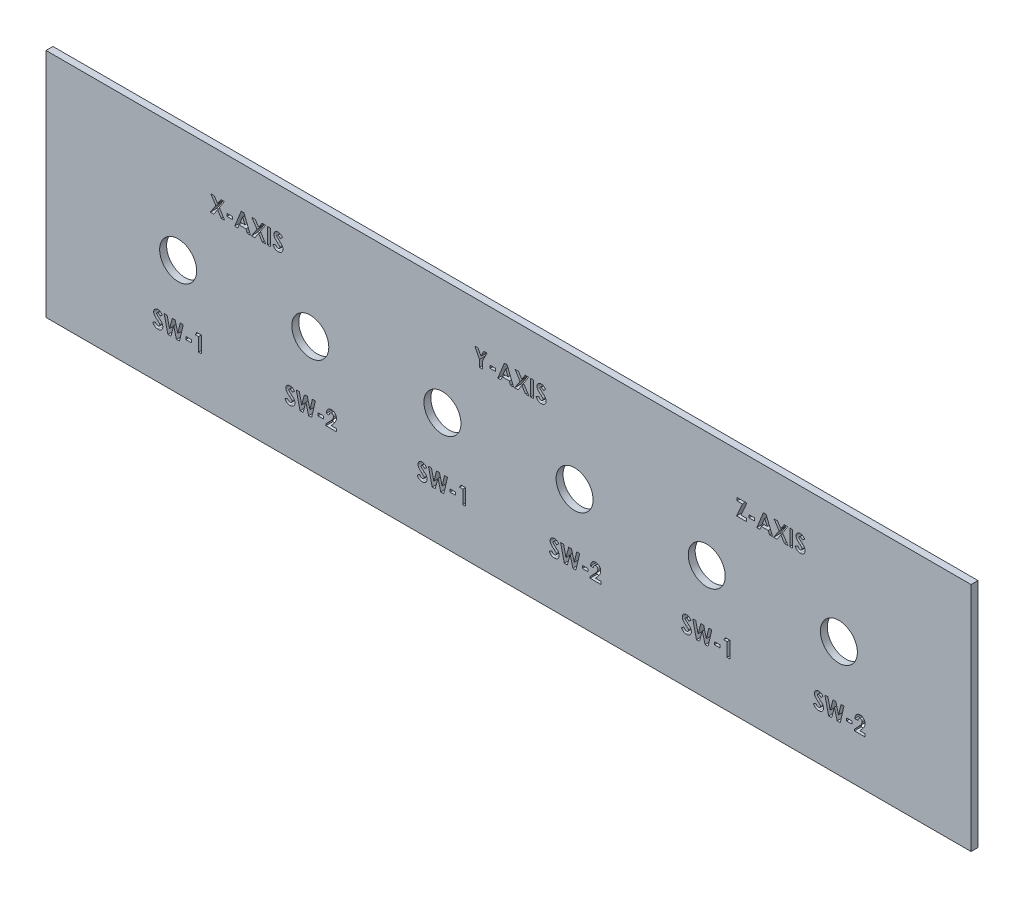
SolidWorks part; units mm, degrees
ref_plane "Front Plane" through (0, 0, 0) normal (0, 0, 1) x (1, 0, 0)
ref_plane "Top Plane" through (0, 0, 0) normal (0, 1, 0) x (1, 0, 0)
ref_plane "Right Plane" through (0, 0, 0) normal (1, 0, 0) x (0, 0, -1)
sketch "Sketch1" plane through (0, 0, 0) normal (0, 0, 1) x (1, 0, 0)
  line L1 (-200, -50) -> (200, -50)
  line L2 (-200, -50) -> (-200, 50)
  line L3 (-200, 50) -> (200, 50)
  line L4 (200, -50) -> (200, 50)
  point P5 (0, 50)
  point P6 (200, 0)
  dimension "D1" = 400
  dimension "D2" = 100
extrude "Boss-Extrude1" add sketch "Sketch1" along normal blind 3
sketch "Sketch2" plane through (0, 0, 3) normal (0, 0, 1) x (1, 0, 0)
  line L0 (-150.8571, 0) -> (-77.7171, 0) construction
  line L1 (-142.8571, 0) -> (-85.7171, 0) construction
  line L2 (-200, 50) -> (-200, -50) construction
  line L3 (-36.5771, 0) -> (36.5629, 0) construction
  line L4 (77.7029, 0) -> (150.8429, 0) construction
  line L5 (-114.2871, -1000) -> (-114.2871, 49000) construction
  line L6 (0, -1000) -> (0, 49000) construction
  line L7 (114.2729, -1000) -> (114.2729, 49000) construction
  line L8 (-150.8571, 25) -> (-77.7171, 25) construction
  line L9 (-36.57, 25) -> (36.57, 25) construction
  line L10 (150.8571, 25) -> (77.7171, 25) construction
  line L11 (200, 50) -> (-200, 50) construction
  line L12 (-160.8541, -30) -> (-124.8602, -30) construction
  line L13 (-103.7141, -30) -> (-67.7202, -30) construction
  line L14 (-46.5741, -30) -> (-10.5802, -30) construction
  line L15 (10.5659, -30) -> (46.5598, -30) construction
  line L16 (67.7059, -30) -> (103.6998, -30) construction
  line L17 (124.8459, -30) -> (160.8398, -30) construction
  line L18 (-160.8541, -30) -> (-103.7141, -30) construction
  circle A0 centre (-142.8571, 0) radius 8
  circle A1 centre (-85.7171, 0) radius 8
  circle A2 centre (-28.5771, 0) radius 8
  circle A3 centre (28.5629, 0) radius 8
  circle A4 centre (85.7029, 0) radius 8
  circle A5 centre (142.8429, 0) radius 8
  text T0 "<b>X-AXIS</b>" font "Century Gothic" height 7
  text T1 "<b>Y-AXIS</b>" font "Century Gothic" height 7
  text T2 "<b>Z-AXIS</b>" font "Century Gothic" height 7
  text T3 "<b>SW-1</b>" font "Century Gothic" height 7
  text T4 "<b>SW-2</b>" font "Century Gothic" height 7
  text T5 "<b>SW-1</b>" font "Century Gothic" height 7
  text T6 "<b>SW-1</b>" font "Century Gothic" height 7
  text T7 "<b>SW-2</b>" font "Century Gothic" height 7
  text T8 "<b>SW-2</b>" font "Century Gothic" height 7
  point P26 (-114.2871, 0)
  point P31 (114.2729, 0)
  point P34 (-114.2871, 25)
  point P37 (0, 25)
  point P49 (-142.8571, -30)
  dimension "D1" = 16
  dimension "D3" = 57.14
  dimension "D4" = 57.1429
  dimension "D5" = 25
  dimension "D6" = 30
  dimension "D8" = 57.14
  dimension "D2" = 6
  dimension "D7" = 6
extrude "Cut-Extrude1" cut sketch "Sketch2" against normal through all
